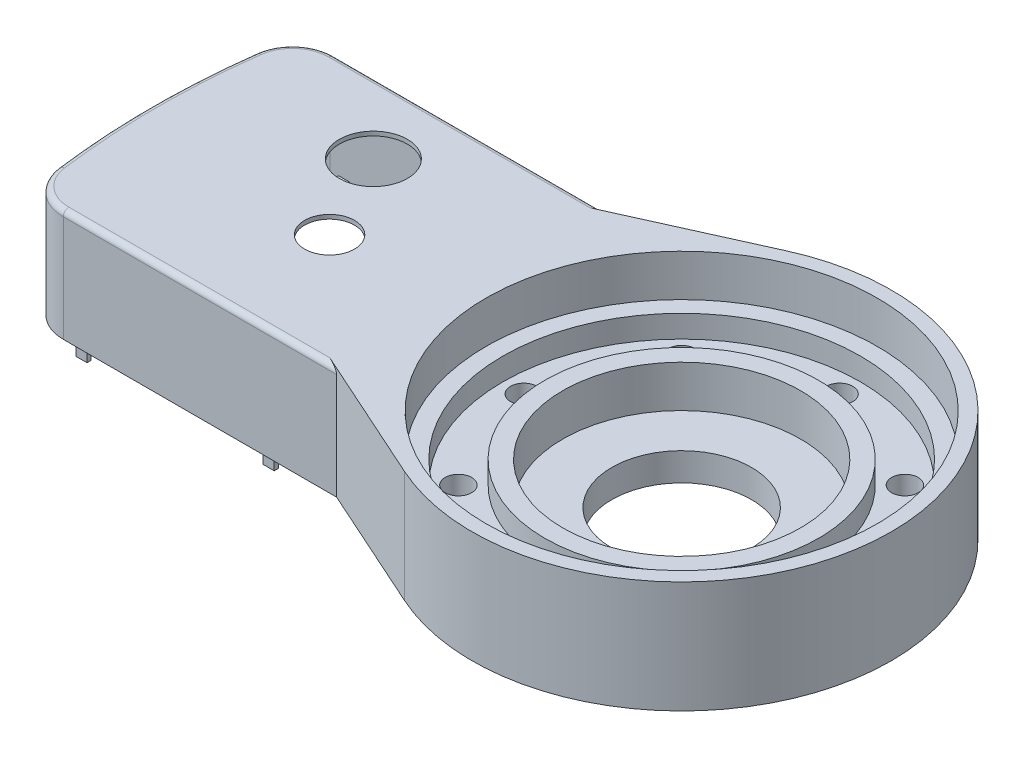
SolidWorks part; units mm, degrees
material "Gray Cast Iron"
ref_plane "Front Plane" through (0, 0, 0) normal (0, 0, 1) x (1, 0, 0)
ref_plane "Top Plane" through (0, 0, 0) normal (0, 1, 0) x (1, 0, 0)
ref_plane "Right Plane" through (0, 0, 0) normal (1, 0, 0) x (0, 0, -1)
sketch "Sketch1" plane through (0, 0, 0) normal (0, 1, 0) x (1, 0, 0)
  line L0 (0, 0) -> (-170.4217, 0) construction
  line L4 (-75, -48.5) -> (-30.7695, -68.3976)
  line L5 (-172.8328, 48.5) -> (-75, 48.5)
  line L6 (-172.8328, -48.5) -> (-75, -48.5)
  line L7 (-75, 48.5) -> (-30.7695, 68.3976)
  arc A5 (-187.7078, 35.4327) -> (-187.7078, -35.4327) centre (85, 0) ccw
  arc A6 (-187.7078, 35.4327) -> (-172.8328, 48.5) centre (-172.8328, 33.5) cw
  arc A7 (-187.7078, -35.4327) -> (-172.8328, -48.5) centre (-172.8328, -33.5) ccw
  arc A9 (-30.7695, -68.3976) -> (-30.7695, 68.3976) centre (0, 0) ccw
  point P2 (-190, 0)
  dimension "D2" = 550
  dimension "D3" = 15
  dimension "D4" = 48.5
  dimension "D1" = 75
  dimension "D6" = 75
  dimension "D7" = 115
extrude "Boss-Extrude1" add sketch "Sketch1" along normal blind 40
sketch "Sketch2" plane through (0, 40, 0) normal (0, 1, 0) x (1, 0, 0)
  circle A3 centre (0, 0) radius 70
  dimension "D4" = 140
extrude "Cut-Extrude1" cut sketch "Sketch2" against normal blind 15
sketch "Sketch3" plane through (0, 25, 0) normal (0, 1, 0) x (1, 0, 0)
  circle A0 centre (0, 0) radius 56.5 construction
  circle A1 centre (56.5, 0) radius 4.75
  circle A2 centre (39.9515, -39.9515) radius 4.75
  circle A3 centre (0, -56.5) radius 4.75
  circle A4 centre (-39.9515, -39.9515) radius 4.75
  circle A5 centre (-56.5, 0) radius 4.75
  circle A6 centre (-39.9515, 39.9515) radius 4.75
  circle A7 centre (0, 56.5) radius 4.75
  circle A8 centre (39.9515, 39.9515) radius 4.75
  circle A9 centre (0, 0) radius 49
  circle A10 centre (0, 0) radius 64
  point P22 (0, 0)
  dimension "D1" = 113
  dimension "D2" = 9.5
  dimension "D4" = 128
  dimension "D5" = 98
  dimension "D3" = 8
extrude "Cut-Extrude2" cut sketch "Sketch3" against normal blind 8
extrude "Cut-Extrude3" cut sketch "Sketch3<2>" against normal through all contours A7 | A6 | A4 | A2 | A1 | A8 | A5 | A3 region at (56.5, 25, 0) region at (39.9515, 25, 39.9515) region at (-39.9515, 25, 39.9515) region at (-39.9515, 25, -39.9515) region at (0, 25, -56.5) region at (39.9515, 25, -39.9515)
sketch "Sketch3<2>" plane through (0, 25, 0) normal (0, 1, 0) x (1, 0, 0) same geometry as "Sketch3"
sketch "Sketch4" plane through (0, 25, 0) normal (0, 1, 0) x (1, 0, 0)
  circle A0 centre (0, 0) radius 25
  dimension "D1" = 50
extrude "Cut-Extrude4" cut sketch "Sketch4" against normal blind 25
sketch "Sketch5" plane through (0, 25, 0) normal (0, 1, 0) x (1, 0, 0)
  circle A0 centre (0, 0) radius 42.5685
extrude "Cut-Extrude5" cut sketch "Sketch5" against normal blind 15
sketch "Sketch6" plane through (0, 0, 0) normal (0, -1, 0) x (1, 0, 0)
  line L0 (-75, 53.26) -> (-75, -53.26)
  line L5 (-171.9419, 53.26) -> (-75, 53.26)
  line L7 (-75, -53.26) -> (-171.9419, -53.26)
  line L8 (-76.5, 53.26) -> (-76.5, -53.26) construction
  line L9 (-171.9419, 53.26) -> (-76.5, 53.26) construction
  line L10 (-76.5, -53.26) -> (-171.9419, -53.26) construction
  line L11 (-75, 54.76) -> (-75, -54.76) construction
  line L12 (-75, -54.76) -> (-171.9419, -54.76) construction
  line L13 (-171.9419, 54.76) -> (-75, 54.76) construction
  arc A6 (-185.2831, -41.8244) -> (-171.9419, -53.26) centre (-171.9419, -39.76) ccw
  arc A7 (-185.2831, 41.8244) -> (-185.2831, -41.8244) centre (85, 0) ccw
  arc A8 (-171.9419, 53.26) -> (-185.2831, 41.8244) centre (-171.9419, 39.76) ccw
  arc A9 (-186.7655, -42.0538) -> (-171.9419, -54.76) centre (-171.9419, -39.76) ccw construction
  arc A10 (-186.7655, 42.0538) -> (-186.7655, -42.0538) centre (85, 0) ccw construction
  arc A11 (-171.9419, 54.76) -> (-186.7655, 42.0538) centre (-171.9419, 39.76) ccw construction
  dimension "D1" = 1.5
extrude "Cut-Extrude6" cut sketch "Sketch6" against normal offset from surface (38.5 mm away) 1.5 up to face at (0, 40, 70)
sketch "Sketch7" plane through (0, 40, 0) normal (0, 1, 0) x (1, 0, 0)
  circle A0 centre (-133.2846, 22.9348) radius 12.1711
  circle A1 centre (-117.6149, -8.4047) radius 8.9235
extrude "Cut-Extrude7" cut sketch "Sketch7" against normal blind 21.5
sketch "Sketch9" plane through (-75, 0, 0) normal (-1, 0, 0) x (0, 0, 1)
  line L1 (-48.5, 38.5) -> (48.5, 38.5)
  line L2 (-48.5, 38.5) -> (-48.5, 0)
  line L3 (-48.5, 0) -> (48.5, 0)
  line L4 (48.5, 38.5) -> (48.5, 0)
extrude "Cut-Extrude8" cut sketch "Sketch9" along normal through all
sketch "Sketch10" plane through (0, 38.5, 0) normal (0, -1, 0) x (1, 0, 0)
  line L0 (-172.8328, -48.5) -> (-75, -48.5) construction
  line L1 (-75, 48.5) -> (-172.8328, 48.5) construction
  line L2 (-172.8328, -48.5) -> (-75, -48.5)
  line L3 (-75, 48.5) -> (-172.8328, 48.5)
  line L4 (-75, 47) -> (-172.8328, 47)
  line L5 (-172.8328, -47) -> (-75, -47)
  line L6 (-75, 48.5) -> (-75, 47)
  line L7 (-75, -47) -> (-75, -48.5)
  arc A0 (-187.7078, -35.4327) -> (-172.8328, -48.5) centre (-172.8328, -33.5) ccw construction
  arc A1 (-187.7078, 35.4327) -> (-187.7078, -35.4327) centre (85, 0) ccw construction
  arc A2 (-172.8328, 48.5) -> (-187.7078, 35.4327) centre (-172.8328, 33.5) ccw construction
  arc A3 (-187.7078, -35.4327) -> (-172.8328, -48.5) centre (-172.8328, -33.5) ccw
  arc A4 (-187.7078, 35.4327) -> (-187.7078, -35.4327) centre (85, 0) ccw
  arc A5 (-172.8328, 48.5) -> (-187.7078, 35.4327) centre (-172.8328, 33.5) ccw
  arc A6 (-172.8328, 47) -> (-186.2203, 35.2394) centre (-172.8328, 33.5) ccw
  arc A7 (-186.2203, 35.2394) -> (-186.2203, -35.2394) centre (85, 0) ccw
  arc A8 (-186.2203, -35.2394) -> (-172.8328, -47) centre (-172.8328, -33.5) ccw
  dimension "D1" = 1.5
extrude "Boss-Extrude2" add sketch "Sketch10" along normal up to surface (38.5 mm away) up to face at (-26.4424, 0, 0)
fillet "Fillet1" radius 2 1 edges at (-190, 40, 0) tangent propagation no
fillet "Fillet2" radius 2 4 edges at (-123.9164, 40, -48.5) (-123.9164, 40, 48.5) (-179.3914, 40, -46.9902) (-179.3914, 40, 46.9902)
sketch "Sketch11" plane through (0, 0, -47) normal (0, 0, 1) x (1, 0, 0)
  line L0 (-75, 0) -> (-172.8328, 0) construction
  line L1 (-169.8328, 4.5) -> (-165.8328, 4.5)
  line L2 (-169.8328, 4.5) -> (-169.8328, -4.5)
  line L3 (-169.8328, -4.5) -> (-165.8328, -4.5)
  line L4 (-165.8328, 4.5) -> (-165.8328, -4.5)
  line L5 (-169.8328, 4.5) -> (-165.8328, -4.5) construction
  line L6 (-169.8328, -4.5) -> (-165.8328, 4.5) construction
  line L7 (-172.8328, 38) -> (-172.8328, 0) construction
  line L8 (-102.8328, 4.5) -> (-98.8328, 4.5)
  line L9 (-102.8328, 4.5) -> (-102.8328, -4.5)
  line L10 (-102.8328, -4.5) -> (-98.8328, -4.5)
  line L11 (-98.8328, 4.5) -> (-98.8328, -4.5)
  line L12 (-102.8328, 4.5) -> (-98.8328, -4.5) construction
  line L13 (-102.8328, -4.5) -> (-98.8328, 4.5) construction
  point P0 (-167.8328, 0)
  point P7 (-100.8328, 0)
  dimension "D1" = 4
  dimension "D2" = 4
  dimension "D3" = 9
  dimension "D4" = 9
  dimension "D5" = 63
  dimension "D6" = 3
extrude "Boss-Extrude3" add sketch "Sketch11" along normal blind 1.5
mirror "Mirror1" about plane through (0, 0, 0) normal (0, 0, 1) of "Boss-Extrude3"
sketch "Sketch12" plane through (0, 0, 0) normal (0, -1, 0) x (1, 0, 0)
  line L1 (-21, 21) -> (21, 21) construction
  line L2 (-21, 21) -> (-21, -21) construction
  line L3 (-21, -21) -> (21, -21) construction
  line L4 (21, 21) -> (21, -21) construction
  line L5 (-21, 21) -> (21, -21) construction
  line L6 (-21, -21) -> (21, 21) construction
  circle A0 centre (21, 21) radius 2
  circle A1 centre (-21, 21) radius 2
  circle A2 centre (21, -21) radius 2
  circle A3 centre (-21, -21) radius 2
  point P0 (0, 0)
  dimension "D3" = 4
  dimension "D1" = 42
  dimension "D2" = 42
extrude "Cut-Extrude9" cut sketch "Sketch12" against normal blind 4
